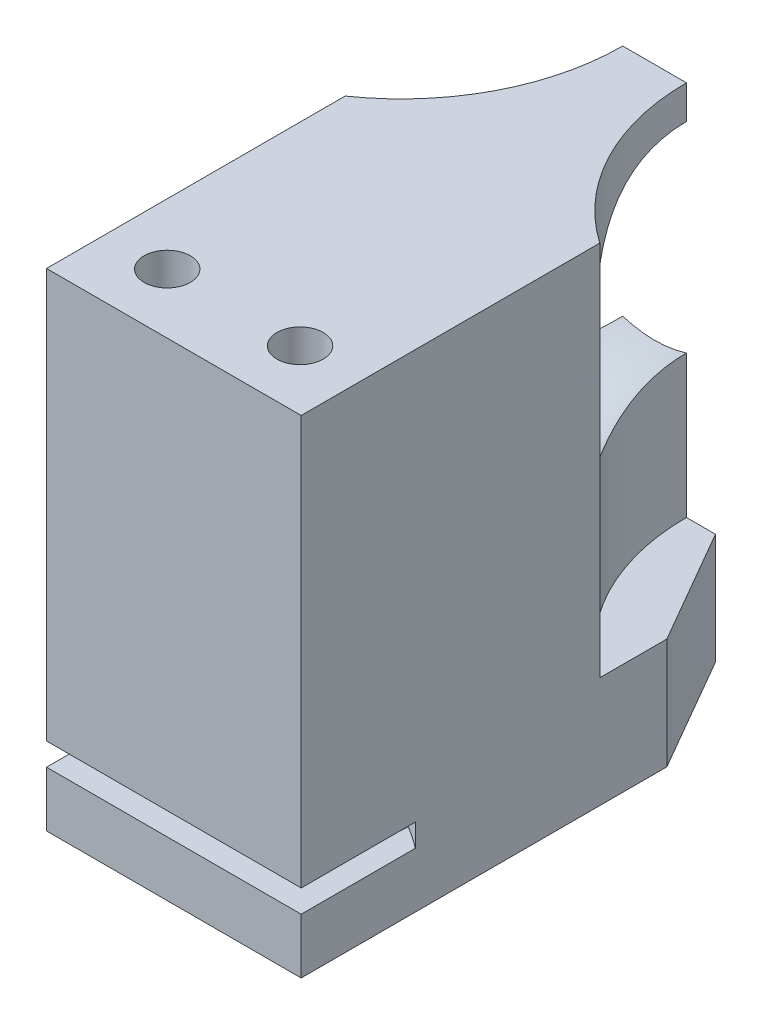
SolidWorks part; units mm, degrees
ref_plane "Front Plane" through (0, 0, 0) normal (0, 0, 1) x (1, 0, 0)
ref_plane "Top Plane" through (0, 0, 0) normal (0, 1, 0) x (1, 0, 0)
ref_plane "Right Plane" through (0, 0, 0) normal (1, 0, 0) x (0, 0, -1)
sketch "Sketch1" plane through (0, 0, 0) normal (0, 1, 0) x (1, 0, 0)
  line L1 (-14.605, 0) -> (14.605, 0)
  line L2 (-14.605, 0) -> (-14.605, -55.1434)
  line L3 (-14.605, -55.1434) -> (14.605, -55.1434)
  line L4 (14.605, 0) -> (14.605, -55.1434)
  point P5 (0, 0)
  dimension "D1" = 29.21
  dimension "D2" = 55.1434
extrude "Boss-Extrude1" add sketch "Sketch1" along normal blind 55.88
ref_axis "Axis1" through (14.605, 0, 0) along (-1, 0, 0)
sketch "Sketch2" plane through (0, 0, 0) normal (0, 0, -1) x (-1, 0, 0)
  circle A0 centre (0, 40.5384) radius 12.065
  dimension "D1" = 24.13
  dimension "D2" = 40.5384
revolve "Cut-Revolve1" cut sketch "Sketch2" angle 90 about axis through (14.605, 0, 0) along (-1, 0, 0) reverse direction yes
sketch "Sketch3" plane through (0, 55.88, 0) normal (0, 1, 0) x (1, 0, 0)
  line L0 (14.605, 0) -> (-14.605, 0) construction
  line L1 (0, 0) -> (0, -133.4577) construction
  circle A0 centre (-29.0576, 0) radius 25.4
  circle A1 centre (29.0576, 0) radius 25.4
  dimension "D2" = 50.8
  dimension "D1" = 29.0576
extrude "Cut-Extrude1" cut sketch "Sketch3" against normal blind 43.18
sketch "Sketch4" plane through (-14.605, 0, 0) normal (-1, 0, 0) x (0, 0, 1)
  line L0 (54.5756, 0) -> (60.96, 0)
  line L1 (60.96, 0) -> (60.96, 60.96)
  line L2 (60.96, 60.96) -> (0, 60.96)
  line L3 (0, 60.96) -> (0, 54.5756)
  circle A0 centre (0, 0) radius 52.0356 construction
  circle A1 centre (0, 0) radius 54.5756
  line M5 (20.8874, 55.88) -> (20.8874, 12.7)
  line M6 (0, 0) -> (55.1434, 0)
  line M7 (55.1434, 0) -> (55.1434, 55.88)
  line M8 (55.1434, 55.88) -> (20.8874, 55.88)
  dimension "D1" = 2.54
  dimension "D2" = 60.96
  dimension "D3" = 60.96
extrude "Cut-Extrude2" [suppressed] cut sketch "Sketch4" against normal through all contours A1 M6 M7 M8 M5 | A1 L0 L1 L2 L3 M5 M8 M7
ref_plane "Plane1" through (0, 8.4328, 0) normal (0, -1, 0) x (-1, 0, 0)
sketch "Sketch6" plane through (0, 8.4328, 0) normal (0, -1, 0) x (-1, 0, 0)
  circle A0 centre (0, -60.8584) radius 23.8125
  circle A1 centre (0, -40.5384) radius 12.065 construction
  dimension "D1" = 20.32
  dimension "D2" = 47.625
extrude "Cut-Extrude4" cut sketch "Sketch6" along normal blind 2.0955 and the other way blind 0.508
sketch "Sketch7" plane through (0, 0, 0) normal (0, -1, 0) x (1, 0, 0)
  line L0 (0, 0) -> (0, 55.1434) construction
  line L1 (-14.605, 55.1434) -> (14.605, 55.1434) construction
  line L2 (14.605, 0) -> (-14.605, 0) construction
  circle A0 centre (0, 6.35) radius 2.6543
  circle A1 centre (-8.128, 21.59) radius 2.6543
  circle A2 centre (8.128, 21.59) radius 2.6543
  dimension "D1" = 5.3086
  dimension "D2" = 8.128
  dimension "D3" = 6.35
  dimension "D4" = 21.59
extrude "Cut-Extrude5" cut sketch "Sketch7" against normal blind 7.62
chamfer "Chamfer1" distance 7.62 angle 60 2 edges at (14.605, 6.35, 0) (-14.605, 6.35, 0) first distance on face at (0, 13.5393, 0)
sketch "Sketch8" plane through (0, 55.88, 0) normal (0, 1, 0) x (1, 0, 0)
  line L0 (0, -55.1434) -> (0, 0) construction
  line L1 (-14.605, -55.1434) -> (14.605, -55.1434) construction
  circle A0 centre (-7.62, -48.2854) radius 2.6543
  circle A1 centre (7.62, -48.2854) radius 2.6543
  dimension "D1" = 5.3086
  dimension "D2" = 7.62
  dimension "D3" = 6.858
extrude "Cut-Extrude6" cut sketch "Sketch8" against normal blind 7.62
sketch "Sketch9" plane through (-14.605, 0, 0) normal (-1, 0, 0) x (0, 0, 1)
  line L0 (55.1434, 55.88) -> (55.1434, 8.9408) construction
  line L1 (20.8874, 55.88) -> (55.1434, 55.88) construction
  circle A0 centre (47.5234, 43.18) radius 2.6543
  circle A1 centre (47.5234, 30.48) radius 2.6543
  point P4 (0, 0)
  point P5 (0, 0)
  dimension "D1" = 7.62
  dimension "D2" = 5.3086
  dimension "D3" = 12.7
  dimension "D4" = 12.7
extrude "Cut-Extrude7" cut sketch "Sketch9" against normal blind 7.62
